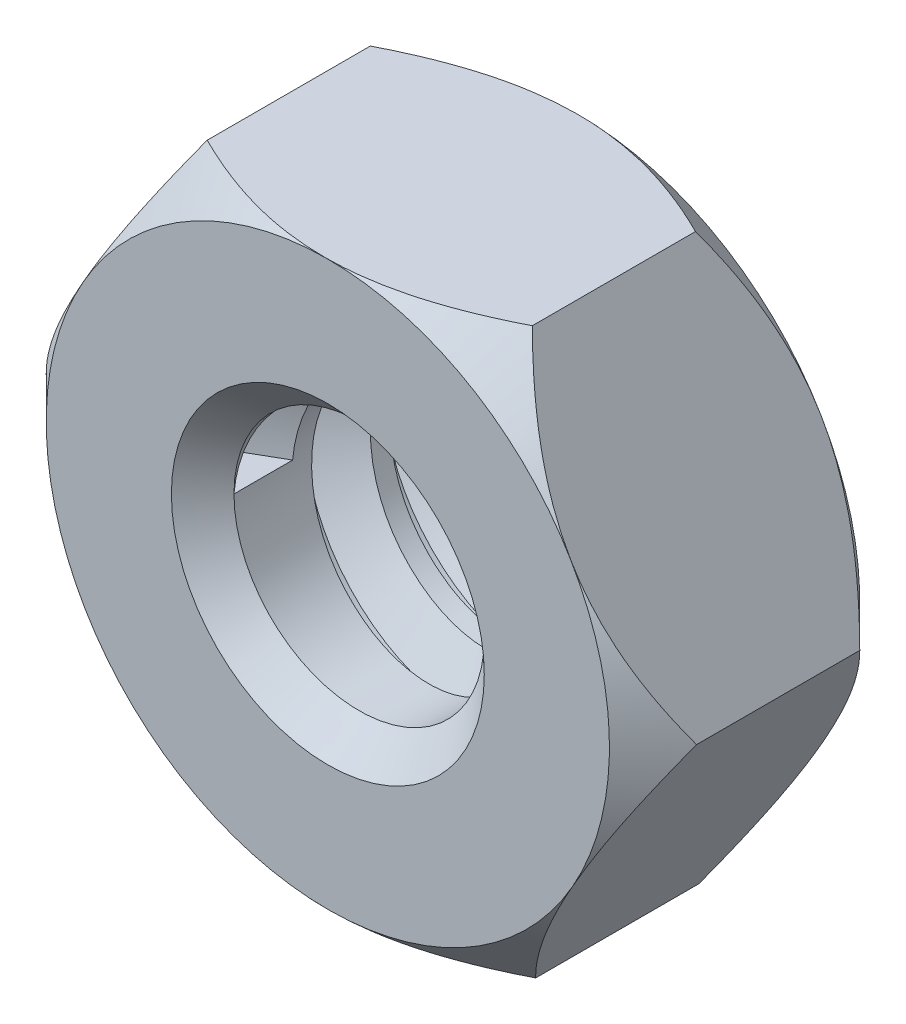
SolidWorks part; units mm, degrees
ref_plane "Front Plane" through (0, 0, 0) normal (0, 0, 1) x (1, 0, 0)
ref_plane "Top Plane" through (0, 0, 0) normal (0, 1, 0) x (1, 0, 0)
ref_plane "Right Plane" through (0, 0, 0) normal (1, 0, 0) x (0, 0, -1)
sketch "Sketch1" plane through (0, 0, 0) normal (0, 0, 1) x (1, 0, 0)
  line L1 (2.6247, -4.4845) -> (5.1961, 0.0308)
  line L2 (5.1961, 0.0308) -> (2.5713, 4.5153)
  line L3 (2.5713, 4.5153) -> (-2.6247, 4.4845)
  line L4 (-2.6247, 4.4845) -> (-5.1961, -0.0308)
  line L5 (-5.1961, -0.0308) -> (-2.5713, -4.5153)
  line L6 (-2.5713, -4.5153) -> (2.6247, -4.4845)
  circle A0 centre (0, 0) radius 4.5 construction
  dimension "D1" = 9
extrude "Boss-Extrude2" add sketch "Sketch1" along normal mid plane 4
sketch "Sketch2" plane through (0, 0, 2) normal (0, 0, 1) x (1, 0, 0)
  circle A0 centre (0, 0) radius 4.5
extrude "Cut-Extrude1" cut sketch "Sketch2" against normal through all draft 45 flip side to cut
mirror "Mirror1" about plane through (0, 0, 0) normal (0, 0, 1) of "Cut-Extrude1"
sketch "Sketch3" plane through (0, 0, 2) normal (0, 0, 1) x (1, 0, 0)
  circle A0 centre (0, 0) radius 2
extrude "Cut-Extrude2" cut sketch "Sketch3" against normal blind 4
chamfer "Chamfer1" distance 0.5 angle 45 2 edges at (2, 0, -2) (2, 0, 2)
thread "Thread2" pitch 1.25 method cut profile "Thread Profile2" start angle 0, offset 0, length 0, pitch 1.25, diameter 4
ref_plane "Plane2" through (-2, 0, 1.5) normal (0, -1, 0) x (-1, 0, 0)
sketch "Thread Profile2" plane through (-2, 0, 1.5) normal (0, -1, 0) x (-1, 0, 0)
  line L0 (0, 0) -> (0, 1.25) construction
  line L1 (0, 0) -> (0.6766, 0.3906)
  line L2 (0.6766, 0.3906) -> (0.6766, 0.5469)
  line L3 (0.6766, 0.5469) -> (0, 0.9375)
  line L4 (0.6766, 0.4687) -> (0, 0.4687) construction
  line L11 (0, 0) -> (0, 0.9375)
  point P2 (0, 0)
  dimension "Pitch" = 1.25
  dimension "Profile_Angle" = 60
  dimension "Profile_Land" = 0.1562
  dimension "Profile_Height" = 0.6766
